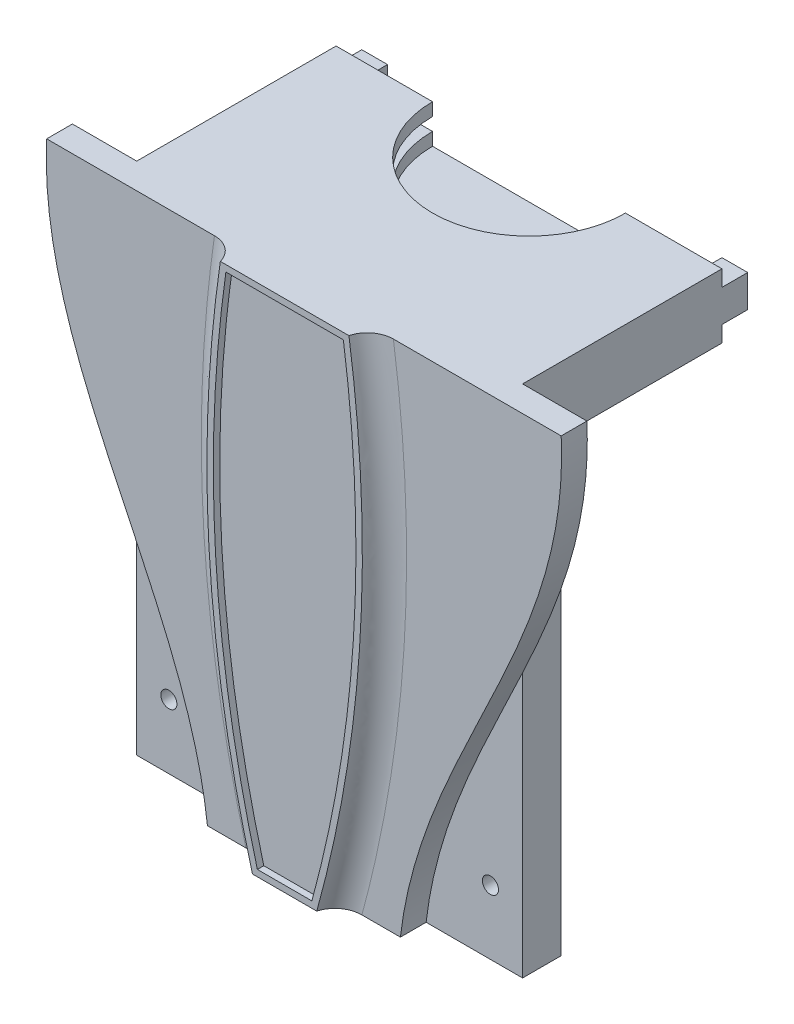
SolidWorks part; units mm, degrees
ref_plane "Front Plane" through (0, 0, 0) normal (0, 0, 1) x (1, 0, 0)
ref_plane "Top Plane" through (0, 0, 0) normal (0, 1, 0) x (1, 0, 0)
ref_plane "Right Plane" through (0, 0, 0) normal (1, 0, 0) x (0, 0, -1)
sketch "Sketch1" plane through (0, 0, 0) normal (0, 0, 1) x (1, 0, 0)
  line L1 (-15, 17.5) -> (15, 17.5)
  line L2 (-15, 17.5) -> (-15, -22.5)
  line L3 (-15, -22.5) -> (15, -22.5)
  line L4 (15, 17.5) -> (15, -22.5)
  dimension "D1" = 30
  dimension "D2" = 40
  dimension "D3" = 15
  dimension "D4" = 17.5
extrude "Boss-Extrude1" add sketch "Sketch1" along normal mid plane 15.5
sketch "Sketch2" plane through (0, 0, -7.75) normal (0, 0, -1) x (-1, 0, 0)
  line L0 (15, -22.5) -> (-15, -22.5) construction
  line L1 (-15, 12.5) -> (15, 12.5)
  line L2 (-15, 12.5) -> (-15, -22.5)
  line L3 (-15, -22.5) -> (15, -22.5)
  line L4 (15, 12.5) -> (15, -22.5)
  dimension "D1" = 35
  dimension "D2" = 30
  dimension "D3" = 15
extrude "Cut-Extrude1" cut sketch "Sketch2" against normal blind 12.5
sketch "Sketch7" plane through (0, 0, -7.75) normal (0, 0, -1) x (-1, 0, 0)
  line L0 (-15, 12.5) -> (-15, 17.5) construction
  line L1 (-15, 16.25) -> (-13, 16.25)
  line L2 (-15, 16.25) -> (-15, 13.7471)
  line L3 (-15, 13.7471) -> (-13, 13.7471)
  line L4 (-13, 16.25) -> (-13, 13.7471)
  line L6 (-15, 17.5) -> (15, 17.5) construction
  line L7 (0, 6.0136) -> (0, 21.6763) construction
  line L8 (15, 13.7471) -> (13, 13.7471)
  line L9 (13, 16.25) -> (13, 13.7471)
  line L10 (15, 16.25) -> (13, 16.25)
  line L11 (15, 16.25) -> (15, 13.7471)
  dimension "D1" = 2.5029
  dimension "D2" = 2
  dimension "D3" = 1.25
extrude "Boss-Extrude5" add sketch "Sketch7" along normal blind 2
sketch "Sketch8" plane through (0, 17.5, 0) normal (0, 1, 0) x (1, 0, 0)
  line L0 (15, 7.75) -> (-15, 7.75) construction
  line L1 (-7.5, 7.75) -> (7.5, 7.75)
  arc A0 (-7.5, 7.75) -> (7.5, 7.75) centre (0, 7.75) ccw
  dimension "D1" = 15
extrude "Cut-Extrude4" cut sketch "Sketch8" against normal blind 3
ref_plane "Plane9" through (0, 16, 0) normal (0, 1, 0) x (1, 0, 0)
sketch "Sketch9" plane through (0, 16, 0) normal (0, 1, 0) x (1, 0, 0)
  line L0 (7.5, 7.75) -> (-7.5, 7.75) construction
  line L1 (-10, 7.75) -> (10, 7.75)
  arc A0 (-10, 7.75) -> (10, 7.75) centre (0, 7.75) ccw
  dimension "D1" = 20
extrude "Cut-Extrude5" cut sketch "Sketch9" against normal mid plane 1
sketch "Sketch10" plane through (0, 0, 7.75) normal (0, 0, 1) x (1, 0, 0)
  line L0 (-20, 17.5) -> (20, 17.5)
  line L1 (-7.5, -22.5) -> (7.5, -22.5)
  line L3 (-15, -22.5) -> (15, -22.5) construction
  line L4 (0, 24.6201) -> (0, -24.7793) construction
  spline S0 degree 3 poles (-20, 17.5) (-20.692, 2.6332) (-9.1606, -8.2395) (-7.5, -22.5) knots 0 0 0 0 1 1 1 1
  spline S1 degree 3 poles (20, 17.5) (20.692, 2.6332) (9.1606, -8.2395) (7.5, -22.5) knots 0 0 0 0 1 1 1 1
  point P4 (-17.42, 3.65)
  point P7 (-10.65, -11.35)
  dimension "D1" = 40
  dimension "D2" = 17.42
  dimension "D3" = 3.65
  dimension "D4" = 7.5
  dimension "D5" = 10.65
  dimension "D6" = 40
  dimension "D7" = 11.35
extrude "Boss-Extrude6" add sketch "Sketch10" along normal blind 2
sketch "Sketch13" plane through (0, 0, 9.75) normal (0, 0, 1) x (1, 0, 0)
  line L0 (-5, 17.5) -> (5, 17.5)
  line L1 (20, 17.5) -> (-20, 17.5) construction
  line L2 (-2.5, -22.5) -> (2.5, -22.5)
  line L3 (-7.5, -22.5) -> (7.5, -22.5) construction
  line L4 (0, 8.2529) -> (0, -8.0351) construction
  spline S0 degree 2 poles (-5, 17.5) (-7.9655, -2.7553) (-2.5, -22.5) knots 0 0 0 1 1 1
  spline S1 degree 2 poles (5, 17.5) (7.9655, -2.7553) (2.5, -22.5) knots 0 0 0 1 1 1
  point P8 (-5.88, -2.26)
  dimension "D2" = 2.5
  dimension "D4" = 5
  dimension "D5" = 5.88
  dimension "D6" = 2.26
extrude "Boss-Extrude8" add sketch "Sketch13" along normal blind 1.5
fillet "Fillet2" radius 2 2 edges
sketch "Sketch4" plane through (0, 0, 4.75) normal (0, 0, -1) x (-1, 0, 0)
  line L0 (0, 19.3589) -> (0, -21.9938) construction
  circle A0 centre (-12.5, -17.5) radius 0.625
  circle A1 centre (12.5, -17.5) radius 0.625
  dimension "D1" = 1.25
  dimension "D3" = 5
  dimension "D2" = 2.5
extrude "Cut-Extrude3" cut sketch "Sketch4" against normal blind 3
sketch "Sketch15" plane through (0, 0, 11.25) normal (0, 0, 1) x (1, 0, 0)
  line L4 (-2.1189, -22) -> (2.1189, -22)
  line L5 (4.5669, 17) -> (-4.5669, 17)
  line L6 (-2.1189, -22) -> (2.1189, -22)
  line L7 (4.5669, 17) -> (-4.5669, 17)
  spline S0 degree 3 poles (3798.0382, 1186.6582) (2024.1995, 776.3347) (-27.8521, 358.363) (-5.157, -5.8331) (-4.7856, -9.0824) (-3.9731, -13.9494) (-3.6589, -15.5734) (67.9216, -341.1349) (1775.6755, -277.9051) (-3357.2452, -1833.0741) knots -27.230842 -27.230842 -27.230842 -27.230842 0.5 0.5 0.75 0.75 0.875 0.875 25.96695 25.96695 25.96695 25.96695 only from (-4.5669, 17) to (-2.1189, -22)
  spline S1 degree 3 poles (-3906.3759, -781.1044) (-2395.5503, -541.9528) (-19.0354, -387.8375) (5.5599, 0.5801) (5.5981, 3.8503) (5.4006, 8.7807) (5.292, 10.4312) (-25.3872, 346.2239) (-1770.564, 496.1376) (3547.8018, 1405.0062) knots -29.093634 -29.093634 -29.093634 -29.093634 0.5 0.5 0.75 0.75 0.875 0.875 26.258226 26.258226 26.258226 26.258226 only from (2.1189, -22) to (4.5669, 17)
  spline S2 degree 3 poles (-4.5669, 17) (-5.4965, 10.4553) (-5.7653, 3.9289) (-5.157, -5.8331) (-4.7856, -9.0824) (-3.9731, -13.9494) (-3.6589, -15.5734) (-2.9493, -18.801) (-2.5539, -20.4052) (-2.1189, -22) knots 0 0 0 0 0.5 0.5 0.75 0.75 0.875 0.875 1 1 1 1
  spline S3 degree 3 poles (2.1189, -22) (3.8583, -15.6228) (4.9418, -9.1813) (5.5599, 0.5801) (5.5981, 3.8503) (5.4006, 8.7807) (5.292, 10.4312) (4.9913, 13.7223) (4.7994, 15.3633) (4.5669, 17) knots 0 0 0 0 0.5 0.5 0.75 0.75 0.875 0.875 1 1 1 1
  dimension "D1" = 0.5
extrude "Cut-Extrude6" cut sketch "Sketch15" against normal blind 0.5
